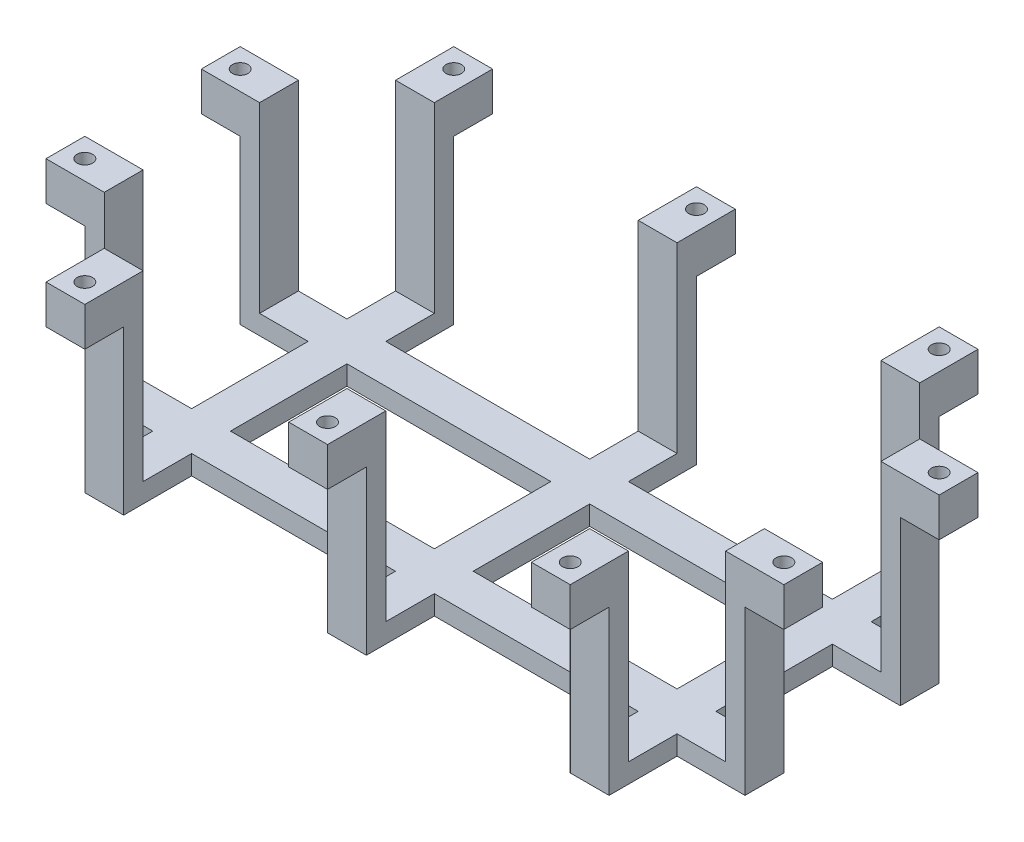
SolidWorks part; units mm, degrees
ref_plane "Front Plane" through (0, 0, 0) normal (0, 0, 1) x (1, 0, 0)
ref_plane "Top Plane" through (0, 0, 0) normal (0, 1, 0) x (1, 0, 0)
ref_plane "Right Plane" through (0, 0, 0) normal (1, 0, 0) x (0, 0, -1)
sketch "Sketch2" plane through (0, 0, 0) normal (0, 1, 0) x (1, 0, 0)
  line L0 (-95, 0) -> (95, 0) construction
  line L1 (-80, -37.5) -> (80, -37.5)
  line L2 (-80, -37.5) -> (-80, 37.5)
  line L3 (-80, 37.5) -> (80, 37.5)
  line L4 (80, -37.5) -> (80, 37.5)
  line L5 (-80, -37.5) -> (80, 37.5) construction
  line L6 (-80, 37.5) -> (80, -37.5) construction
  line L7 (-95, -52.5) -> (95, -52.5)
  line L8 (-95, -52.5) -> (-95, 52.5)
  line L9 (-95, 52.5) -> (95, 52.5)
  line L10 (95, -52.5) -> (95, 52.5)
  line L11 (-95, -52.5) -> (95, 52.5) construction
  line L12 (-95, 52.5) -> (95, -52.5) construction
  line L13 (-80, 37.5) -> (-67.5, 25) construction
  line L14 (-95, 25) -> (95, 25)
  line L15 (-95, 25) -> (-95, 15)
  line L16 (-95, 15) -> (95, 15)
  line L17 (95, 25) -> (95, 15)
  line L18 (0, 52.5) -> (0, -52.5) construction
  line L19 (-67.5, 25) -> (-57.5, 25)
  line L20 (-67.5, 25) -> (-67.5, 52.5)
  line L21 (-67.5, 52.5) -> (-57.5, 52.5)
  line L22 (-57.5, 25) -> (-57.5, 52.5)
  line L23 (-5, 25) -> (5, 25)
  line L24 (-5, 25) -> (-5, 52.5)
  line L25 (-5, 52.5) -> (5, 52.5)
  line L26 (5, 25) -> (5, 52.5)
  line L27 (67.5, 25) -> (67.5, 52.5)
  line L28 (57.5, 25) -> (57.5, 52.5)
  line L29 (-57.5, -25) -> (-57.5, -52.5)
  line L30 (57.5, -25) -> (57.5, -52.5)
  line L31 (67.5, -25) -> (67.5, -52.5)
  line L32 (-5, -52.5) -> (5, -52.5)
  line L33 (5, -25) -> (5, -52.5)
  line L34 (-5, -25) -> (5, -25)
  line L35 (-5, -25) -> (-5, -52.5)
  line L36 (-67.5, -25) -> (-67.5, -52.5)
  line L37 (-95, -15) -> (95, -15)
  line L38 (-95, -25) -> (95, -25)
  line L39 (-67.5, 25) -> (-67.5, -25)
  line L40 (-57.5, 25) -> (-57.5, -25)
  line L41 (-5, 25) -> (-5, -25)
  line L42 (67.5, 25) -> (67.5, -25)
  line L43 (57.5, 25) -> (57.5, -25)
  line L44 (5, 25) -> (5, -25)
  line L45 (-85, -15) -> (-85, -25)
  line L46 (-85, 15) -> (-85, 25)
  line L47 (85, -15) -> (85, -25)
  line L48 (85, 15) -> (85, 25)
  line L49 (-67.5, 42.5) -> (-57.5, 42.5)
  line L50 (5, 42.5) -> (-5, 42.5)
  line L51 (67.5, 42.5) -> (57.5, 42.5)
  line L52 (67.5, -42.5) -> (57.5, -42.5)
  line L53 (5, -42.5) -> (-5, -42.5)
  line L54 (-67.5, -42.5) -> (-57.5, -42.5)
  point P0 (0, 0)
  point P5 (0, 0)
  point P25 (0, 25)
  point P26 (0, 25)
  dimension "D1" = 75
  dimension "D2" = 160
  dimension "D3" = 105
  dimension "D4" = 190
  dimension "D5" = 10
  dimension "D6" = 15
  dimension "D7" = 45
  dimension "D8" = 10
  dimension "D9" = 10
  dimension "D10" = 5
  dimension "D11" = 5
extrude "Boss-Extrude1" add sketch "Sketch2" along normal blind 5 contours L41 L14 L40 L16 | L40 L14 L39 L16 | L40 L16 L39 L37 | L44 L16 L41 L37 | L44 L14 L41 L16 | L41 L37 L40 L38 | L44 L37 L41 L34 | L40 L37 L39 L38 | L37 L44 L38 L43 | L14 L44 L16 L43 | L16 L43 L37 L42 | L14 L43 L16 L42 | L37 L43 L38 L42 | L34 L35 L1 L33 | L38 L30 L1 L31 | L37 L42 L38 L4 | L14 L42 L16 L4 | L14 L26 L3 L24 | L28 L14 L27 L3 | L14 L22 L3 L20 | L39 L14 L2 L16 | L39 L37 L2 L38 | L38 L36 L1 L29 region at (-62.5, 0, 31.25) region at (-73.75, 0, 20) region at (-62.5, 0, 20) region at (0, 0, 31.25) region at (-31.25, 0, 20) region at (-62.5, 0, 0) region at (-73.75, 0, -20) region at (0, 0, 20) region at (-62.5, 0, -20) region at (62.5, 0, 31.25) region at (31.25, 0, 20) region at (0, 0, 0) region at (-31.25, 0, -20) region at (-62.5, 0, -31.25) region at (62.5, 0, 20) region at (0, 0, -20) region at (73.75, 0, 20) region at (62.5, 0, 0) region at (31.25, 0, -20) region at (0, 0, -31.25) region at (62.5, 0, -20) region at (73.75, 0, -20) region at (62.5, 0, -31.25)
extrude "Boss-Extrude2" add sketch "Sketch2<4>" along normal blind 52 contours L36 L54 L29 L1 | L53 L33 L1 L35 | L52 L31 L1 L30 | L47 L37 L4 L38 | L16 L48 L14 L4 | L27 L51 L28 L3 | L26 L50 L24 L3 | L49 L20 L3 L22 | L46 L16 L2 L14 | L37 L45 L38 L2 region at (-62.5, 0, 40) region at (-82.5, 0, 20) region at (0, 0, 40) region at (-82.5, 0, -20) region at (62.5, 0, 40) region at (-62.5, 0, -40) region at (82.5, 0, 20) region at (0, 0, -40) region at (82.5, 0, -20) region at (62.5, 0, -40)
sketch "Sketch2<4>" plane through (0, 0, 0) normal (0, 1, 0) x (1, 0, 0) same geometry as "Sketch2"
extrude "Boss-Extrude3" add sketch "Sketch2<5>" along direction (0, -1, 0) on the side of the normal up to surface (52 mm away) contours L54 L36 L7 L29 | L45 L37 L8 L38 | L16 L46 L14 L8 | L20 L49 L22 L9 | L50 L26 L9 L24 | L51 L27 L9 L28 | L48 L16 L10 L14 | L37 L47 L38 L10 | L31 L52 L30 L7 | L33 L53 L35 L7 region at (-62.5, 0, 47.5) region at (-90, 0, 20) region at (0, 0, 47.5) region at (-90, 0, -20) region at (62.5, 0, 47.5) region at (-62.5, 0, -47.5) region at (90, 0, 20) region at (0, 0, -47.5) region at (90, 0, -20) region at (62.5, 0, -47.5) up to face at (-62.5, 52, 40)
sketch "Sketch2<5>" plane through (0, 0, 0) normal (0, 1, 0) x (1, 0, 0) same geometry as "Sketch2"
extrude "Cut-Extrude1" cut sketch "Sketch2<6>" along normal offset from surface (42 mm away) 10 contours L54 L36 L7 L29 | L45 L37 L8 L38 | L16 L46 L14 L8 | L20 L49 L22 L9 | L50 L26 L9 L24 | L51 L27 L9 L28 | L48 L16 L10 L14 | L37 L47 L38 L10 | L31 L52 L30 L7 | L33 L53 L35 L7 region at (-62.5, 0, 47.5) region at (-90, 0, 20) region at (0, 0, 47.5) region at (-90, 0, -20) region at (62.5, 0, 47.5) region at (-62.5, 0, -47.5) region at (90, 0, 20) region at (0, 0, -47.5) region at (90, 0, -20) region at (62.5, 0, -47.5) up to face at (62.5, 52, -45)
sketch "Sketch2<6>" plane through (0, 0, 0) normal (0, 1, 0) x (1, 0, 0) same geometry as "Sketch2"
sketch "Sketch3" plane through (0, 42, 0) normal (0, -1, 0) x (1, 0, 0)
  line L0 (67.5, -42.5) -> (57.5, -42.5) construction
  line L1 (57.5, -42.5) -> (57.5, -52.5) construction
  line L2 (57.5, -52.5) -> (67.5, -52.5) construction
  line L3 (67.5, -52.5) -> (67.5, -42.5) construction
  line L4 (85, -15) -> (85, -25) construction
  line L5 (85, -25) -> (95, -25) construction
  line L6 (95, -25) -> (95, -15) construction
  line L7 (95, -15) -> (85, -15) construction
  line L8 (85, 15) -> (95, 15) construction
  line L9 (95, 15) -> (95, 25) construction
  line L10 (95, 25) -> (85, 25) construction
  line L11 (85, 25) -> (85, 15) construction
  line L12 (67.5, 42.5) -> (67.5, 52.5) construction
  line L13 (67.5, 52.5) -> (57.5, 52.5) construction
  line L14 (57.5, 52.5) -> (57.5, 42.5) construction
  line L15 (57.5, 42.5) -> (67.5, 42.5) construction
  line L16 (5, 42.5) -> (5, 52.5) construction
  line L17 (5, 52.5) -> (-5, 52.5) construction
  line L18 (-5, 52.5) -> (-5, 42.5) construction
  line L19 (-5, 42.5) -> (5, 42.5) construction
  line L20 (5, -42.5) -> (-5, -42.5) construction
  line L21 (-5, -42.5) -> (-5, -52.5) construction
  line L22 (-5, -52.5) -> (5, -52.5) construction
  line L23 (5, -52.5) -> (5, -42.5) construction
  line L24 (-67.5, -42.5) -> (-67.5, -52.5) construction
  line L25 (-67.5, -52.5) -> (-57.5, -52.5) construction
  line L26 (-57.5, -52.5) -> (-57.5, -42.5) construction
  line L27 (-57.5, -42.5) -> (-67.5, -42.5) construction
  line L28 (-95, -15) -> (-95, -25) construction
  line L29 (-95, -25) -> (-85, -25) construction
  line L30 (-85, -25) -> (-85, -15) construction
  line L31 (-85, -15) -> (-95, -15) construction
  line L32 (-85, 15) -> (-85, 25) construction
  line L33 (-85, 25) -> (-95, 25) construction
  line L34 (-95, 25) -> (-95, 15) construction
  line L35 (-95, 15) -> (-85, 15) construction
  line L36 (-67.5, 42.5) -> (-57.5, 42.5) construction
  line L37 (-57.5, 42.5) -> (-57.5, 52.5) construction
  line L38 (-57.5, 52.5) -> (-67.5, 52.5) construction
  line L39 (-67.5, 52.5) -> (-67.5, 42.5) construction
  line L40 (67.5, -42.5) -> (57.5, -42.5)
  line L41 (57.5, -42.5) -> (57.5, -52.5)
  line L42 (57.5, -52.5) -> (67.5, -52.5)
  line L43 (67.5, -52.5) -> (67.5, -42.5)
  line L44 (85, -15) -> (85, -25)
  line L45 (85, -25) -> (95, -25)
  line L46 (95, -25) -> (95, -15)
  line L47 (95, -15) -> (85, -15)
  line L48 (85, 15) -> (95, 15)
  line L49 (95, 15) -> (95, 25)
  line L50 (95, 25) -> (85, 25)
  line L51 (85, 25) -> (85, 15)
  line L52 (67.5, 42.5) -> (67.5, 52.5)
  line L53 (67.5, 52.5) -> (57.5, 52.5)
  line L54 (57.5, 52.5) -> (57.5, 42.5)
  line L55 (57.5, 42.5) -> (67.5, 42.5)
  line L56 (5, 42.5) -> (5, 52.5)
  line L57 (5, 52.5) -> (-5, 52.5)
  line L58 (-5, 52.5) -> (-5, 42.5)
  line L59 (-5, 42.5) -> (5, 42.5)
  line L60 (5, -42.5) -> (-5, -42.5)
  line L61 (-5, -42.5) -> (-5, -52.5)
  line L62 (-5, -52.5) -> (5, -52.5)
  line L63 (5, -52.5) -> (5, -42.5)
  line L64 (-67.5, -42.5) -> (-67.5, -52.5)
  line L65 (-67.5, -52.5) -> (-57.5, -52.5)
  line L66 (-57.5, -52.5) -> (-57.5, -42.5)
  line L67 (-57.5, -42.5) -> (-67.5, -42.5)
  line L68 (-95, -15) -> (-95, -25)
  line L69 (-95, -25) -> (-85, -25)
  line L70 (-85, -25) -> (-85, -15)
  line L71 (-85, -15) -> (-95, -15)
  line L72 (-85, 15) -> (-85, 25)
  line L73 (-85, 25) -> (-95, 25)
  line L74 (-95, 25) -> (-95, 15)
  line L75 (-95, 15) -> (-85, 15)
  line L76 (-67.5, 42.5) -> (-57.5, 42.5)
  line L77 (-57.5, 42.5) -> (-57.5, 52.5)
  line L78 (-57.5, 52.5) -> (-67.5, 52.5)
  line L79 (-67.5, 52.5) -> (-67.5, 42.5)
  line L80 (-95, 25) -> (-85, 15) construction
  line L81 (-67.5, 52.5) -> (-57.5, 42.5) construction
  line L82 (-5, 52.5) -> (5, 42.5) construction
  line L83 (0, 0) -> (0, 29.2626) construction
  line L84 (0, 0) -> (41.8436, 0) construction
  circle A0 centre (-90, 20) radius 2
  circle A1 centre (-62.5, 47.5) radius 2
  circle A2 centre (0, 47.5) radius 2
  circle A3 centre (62.5, 47.5) radius 2
  circle A4 centre (90, 20) radius 2
  circle A5 centre (90, -20) radius 2
  circle A6 centre (62.5, -47.5) radius 2
  circle A7 centre (0, -47.5) radius 2
  circle A8 centre (-62.5, -47.5) radius 2
  circle A9 centre (-90, -20) radius 2
  dimension "D1" = 4
  dimension "D2" = 4
  dimension "D3" = 4
extrude "Cut-Extrude2" cut sketch "Sketch3" against normal up to surface (10 mm away) contours A8 | A9 | A7 | A6 | A5 | A4 | A3 | A2 | A0 | A1 region at (-90, 42, 20) region at (-62.5, 42, 47.5) region at (0, 42, 47.5) region at (62.5, 42, 47.5) region at (90, 42, 20) region at (90, 42, -20) region at (62.5, 42, -47.5) region at (0, 42, -47.5) region at (-62.5, 42, -47.5) region at (-90, 42, -20) up to face at (-62.5, 52, -45)
